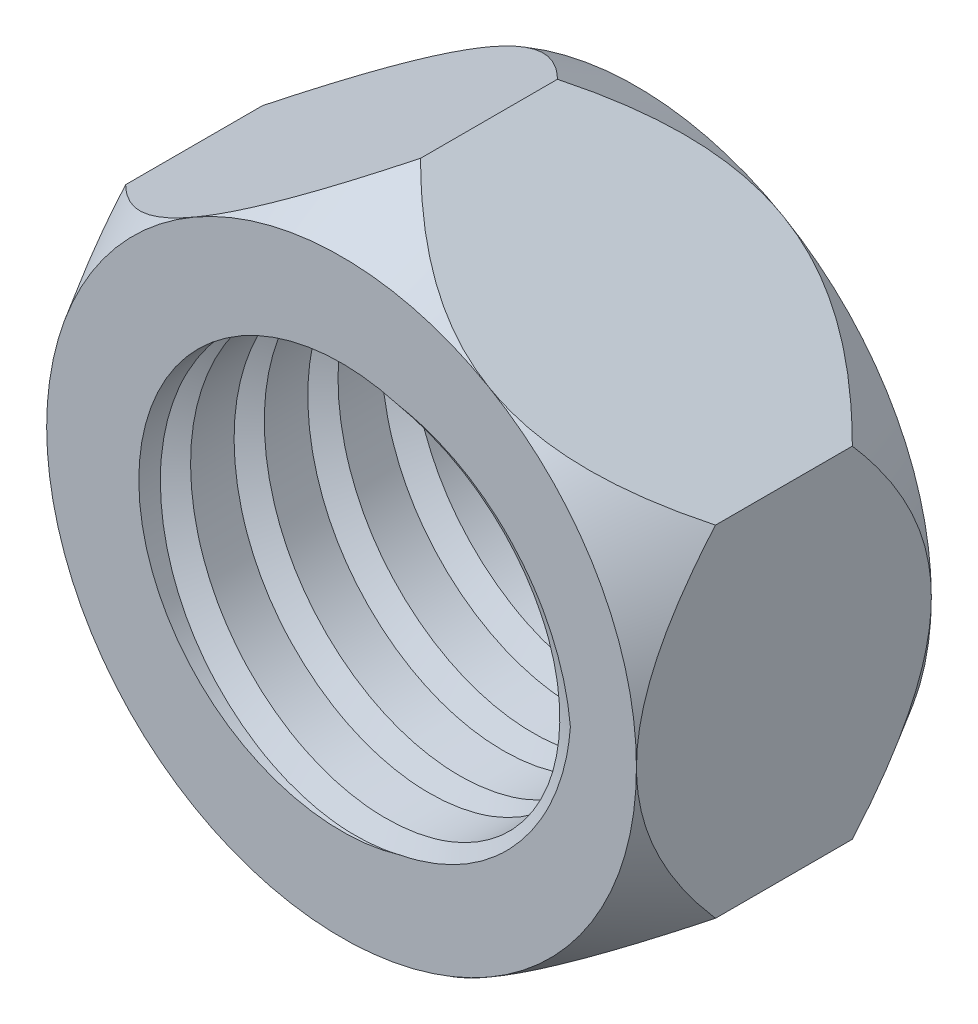
SolidWorks part; units mm, degrees
ref_plane "Ön Düzlem" through (0, 0, 0) normal (0, 0, 1) x (1, 0, 0)
ref_plane "Üst Düzlem" through (0, 0, 0) normal (0, 1, 0) x (1, 0, 0)
ref_plane "Sağ Düzlem" through (0, 0, 0) normal (1, 0, 0) x (0, 0, -1)
sketch "Çizim1" plane through (0, 0, 0) normal (0, 0, 1) x (1, 0, 0)
  line L0 (0, 4.6188) -> (0, -4.6188) construction
  line L1 (0, 4.6188) -> (-4, 2.3094)
  line L2 (-4, 2.3094) -> (-4, -2.3094)
  line L3 (-4, -2.3094) -> (0, -4.6188)
  line L4 (0, -4.6188) -> (4, -2.3094)
  line L5 (4, -2.3094) -> (4, 2.3094)
  line L6 (4, 2.3094) -> (0, 4.6188)
  circle A0 centre (0, 0) radius 4 construction
  dimension "D1" = 8
extrude "Yükseklik-Ekstrüzyon1" add sketch "Çizim1" along normal blind 4
sketch "Çizim2" plane through (0, 0, 4) normal (0, 0, 1) x (1, 0, 0)
  circle A0 centre (0, 0) radius 4
  dimension "D1" = 8
extrude "Kes-Ekstrüzyon1" cut sketch "Çizim2" against normal blind 4 draft 30 flip side to cut
sketch "Çizim3" plane through (0, 0, 0) normal (0, 0, -1) x (-1, 0, 0)
  circle A0 centre (0, 0) radius 4
extrude "Kes-Ekstrüzyon2" cut sketch "Çizim3" against normal blind 4 draft 30 flip side to cut
sketch "Çizim4" plane through (0, 0, 4) normal (0, 0, 1) x (1, 0, 0)
  circle A0 centre (0, 0) radius 2.75
  dimension "D1" = 5.5
extrude "Kes-Ekstrüzyon3" cut sketch "Çizim4" against normal up to next
sketch "Çizim5" plane through (0, 0, 4) normal (0, 0, 1) x (1, 0, 0)
  circle A0 centre (0, 0) radius 2.75
curve "Helis/Spiral1" pitch 1 height 4 radius 2.75 centre (0, 0, 4) axis (0, 0, -1) start towards (1, 0, 0)
ref_plane "Düzlem1" through (2.75, 0, 0) normal (0, -0.9983, -0.0578) x (-1, 0, 0)
sketch "Çizim6" plane through (2.75, 0, 0) normal (0, -0.9983, -0.0578) x (-1, 0, 0)
  line L1 (-0.3543, 0.0013) -> (0.3957, -0.4317)
  line L2 (0.3957, -0.4317) -> (0.3957, 0.4343)
  line L3 (0.3957, 0.4343) -> (-0.3543, 0.0013)
  circle A0 centre (0.1457, 0.0013) radius 0.25 construction
  dimension "D1" = 0.5
sweep "Kes-Süpür2" cut profiles "Çizim6" path "Helis/Spiral1" align with end faces yes
